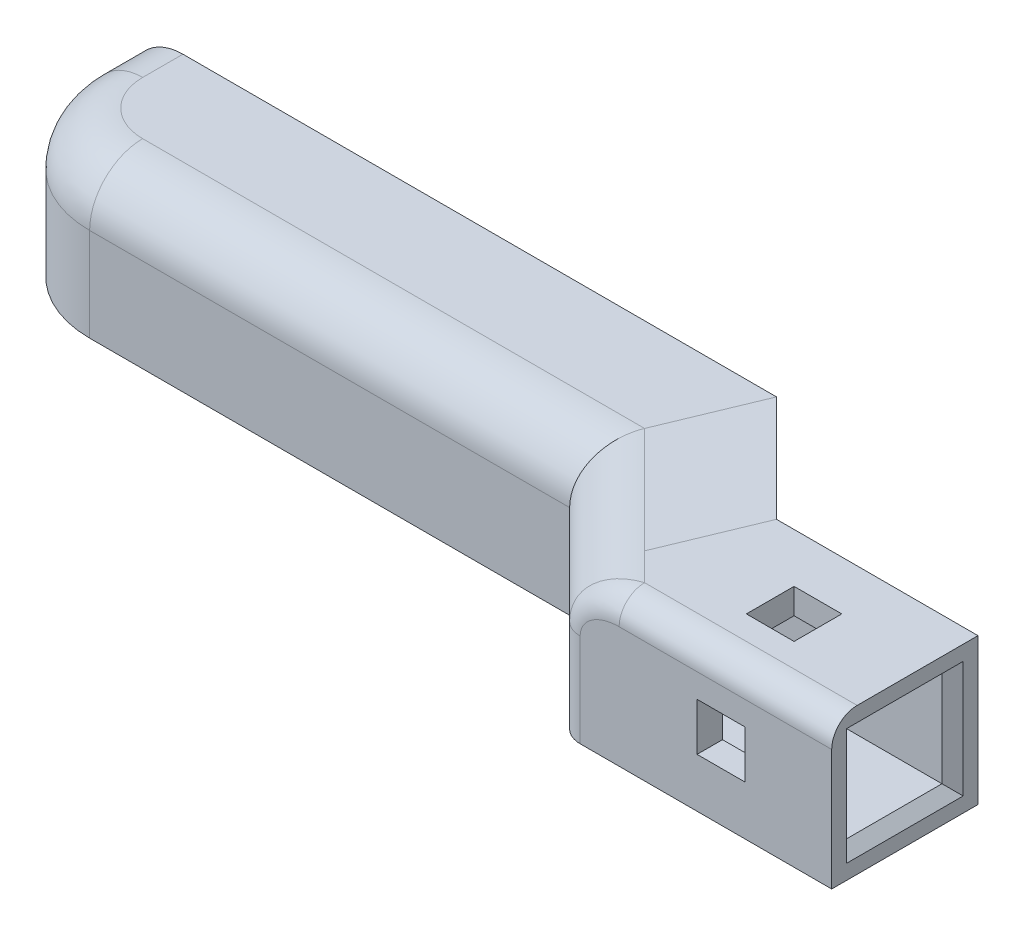
SolidWorks part; units mm, degrees
ref_plane "Front Plane" through (0, 0, 0) normal (0, 0, 1) x (1, 0, 0)
ref_plane "Top Plane" through (0, 0, 0) normal (0, 1, 0) x (1, 0, 0)
ref_plane "Right Plane" through (0, 0, 0) normal (1, 0, 0) x (0, 0, -1)
sketch "Sketch1" plane through (0, 0, 0) normal (1, 0, 0) x (0, 0, -1)
  line L0 (-2.4, 11.4) -> (11.4, 11.4)
  line L1 (0, 0) -> (9, 0)
  line L2 (0, 0) -> (0, 9)
  line L3 (0, 9) -> (9, 9)
  line L4 (9, 0) -> (9, 9)
  line L5 (11.4, -2.4) -> (11.4, 11.4)
  line L6 (-2.4, -2.4) -> (11.4, -2.4)
  line L7 (-2.4, -2.4) -> (-2.4, 11.4)
  dimension "D1" = 9
  dimension "D2" = 2.4
sketch "Sketch2" plane through (0, 0, 0) normal (0, 1, 0) x (1, 0, 0)
  line L1 (0, 9) -> (-20, 9)
  line L2 (-20, 9) -> (-20, 19) construction
  line L3 (-20, 19) -> (-30, 19) construction
  line L4 (-20, 9) -> (-30, 19)
  line L5 (-30, 19) -> (-90, 19)
  dimension "D2" = 10
  dimension "D3" = 60
  dimension "D4" = 20
sweep "Sweep1" add profiles "Sketch1" path "Sketch2"
sketch "Sketch6" plane through (-90, 0, 0) normal (-1, 0, 0) x (0, 0, 1)
  line L1 (-10, 9) -> (-19, 9)
  line L2 (-10, 9) -> (-10, 0)
  line L3 (-10, 0) -> (-19, 0)
  line L4 (-19, 9) -> (-19, 0)
extrude "Boss-Extrude1" add sketch "Sketch6" against normal up to next
fillet "Fillet1" radius 10 1 edges at (-90, 4.5, -7.6)
fillet "Fillet2" radius 5 4 edges at (-90, 11.4, -19.5) (-87.0711, 11.4, -10.5289) (-29.722, 11.4, -2.6) (-57.361, 11.4, -7.6)
fillet "Fillet3" radius 2.4 3 edges at (-8.8255, 11.4, 2.4) (-22.651, 9.9355, 2.4) (-24.722, 2, 2.4)
sketch "Sketch7" plane through (0, 0, -9) normal (0, 0, 1) x (1, 0, 0)
  line L1 (-8.2, 6.75) -> (-12.7, 6.75)
  line L2 (-8.2, 6.75) -> (-8.2, 2.25)
  line L3 (-8.2, 2.25) -> (-12.7, 2.25)
  line L4 (-12.7, 6.75) -> (-12.7, 2.25)
  line L5 (-10.45, 6.75) -> (-10.45, 9) construction
  line L7 (-10.45, 2.25) -> (-10.45, 0) construction
  line L9 (0, 9) -> (-20, 9) construction
  line L10 (0, 0) -> (-20, 0) construction
  line L11 (0, 9) -> (0, 0) construction
  dimension "D1" = 4.5
  dimension "D2" = 8.2
extrude "Cut-Extrude1" cut sketch "Sketch7" against normal up to next contours L2 L1 L4 L3
chamfer "Chamfer1" distance 1 angle 45 4 edges at (0, 4.5, -9) (0, 9, -4.5) (0, 4.5, 0) (0, 0, -4.5)
ref_plane "Plane1" through (-1, 0, 0) normal (0, 0, -1) x (-1, 0, 0)
sketch "Sketch8" plane through (-1, 0, 0) normal (0, 0, -1) x (-1, 0, 0)
  line L0 (0, 9) -> (22.7279, 9) construction
  line L1 (11.7, 6.75) -> (7.2, 6.75)
  line L2 (11.7, 6.75) -> (11.7, 2.25)
  line L3 (11.7, 2.25) -> (7.2, 2.25)
  line L4 (7.2, 6.75) -> (7.2, 2.25)
  line L5 (9.45, 6.75) -> (9.45, 9) construction
  line L6 (0, 0) -> (22.7279, 0) construction
  line L7 (9.45, 2.25) -> (9.45, 0) construction
  line L8 (-1, 9) -> (-1, -2.4) construction
  dimension "D1" = 4.5
  dimension "D2" = 8.2
sketch "Sketch9" plane through (0, 0, 0) normal (0, 1, 0) x (1, 0, 0)
  line L0 (-1, 9) -> (-20, 9) construction
  line L1 (-8.2, 6.75) -> (-12.7, 6.75)
  line L2 (-8.2, 6.75) -> (-8.2, 2.25)
  line L3 (-8.2, 2.25) -> (-12.7, 2.25)
  line L4 (-12.7, 6.75) -> (-12.7, 2.25)
  line L5 (-10.45, 6.75) -> (-10.45, 9) construction
  line L6 (-1, 0) -> (-23.7279, 0) construction
  line L7 (-10.45, 2.25) -> (-10.45, 0) construction
  line L8 (0, 10) -> (0, -1) construction
  dimension "D1" = 4.5
  dimension "D2" = 8.2
sketch "Sketch10" plane through (0, 9, 0) normal (0, -1, 0) x (-1, 0, 0)
  line L0 (1, 0) -> (23.7279, 0) construction
  line L1 (12.7, 6.75) -> (8.2, 6.75)
  line L2 (12.7, 6.75) -> (12.7, 2.25)
  line L3 (12.7, 2.25) -> (8.2, 2.25)
  line L4 (8.2, 6.75) -> (8.2, 2.25)
  line L5 (10.45, 6.75) -> (10.45, 9) construction
  line L6 (1, 9) -> (20, 9) construction
  line L7 (10.45, 2.25) -> (10.45, 0) construction
  line L8 (0, -1) -> (0, 10) construction
  dimension "D1" = 4.5
  dimension "D2" = 8.2
extrude "Cut-Extrude2" cut sketch "Sketch8" against normal up to next
extrude "Cut-Extrude3" cut sketch "Sketch10" against normal up to next
extrude "Cut-Extrude4" cut sketch "Sketch9" against normal up to next
equation "\"Tube_ID\"= 9"
equation "\"D1@Sketch1\"=\"Tube_ID\""
equation "\"wall_Thickness\"=2.4"
equation "\"D2@Sketch1\"=\"wall_Thickness\""
equation "\"Extension_Length\"=60"
equation "\"D3@Sketch2\"=\"Extension_Length\""
equation "\"Offset_Amount\"=10"
equation "\"D2@Sketch2\"=\"Offset_Amount\""
equation "\"Socket_Depth\"=20"
equation "\"D4@Sketch2\"=\"Socket_Depth\""
equation "\"Overall_Length\"= \"Extension_Length\" + \"Offset_Amount\" + \"Socket_Depth\""
equation "\"hole_from_edge\"=8.2"
equation "\"D2@Sketch7\"=\"hole_from_edge\""
equation "\"D2@Sketch8\"=\"hole_from_edge\""
equation "\"D2@Sketch9\"=\"hole_from_edge\""
equation "\"D2@Sketch10\"=\"hole_from_edge\""
